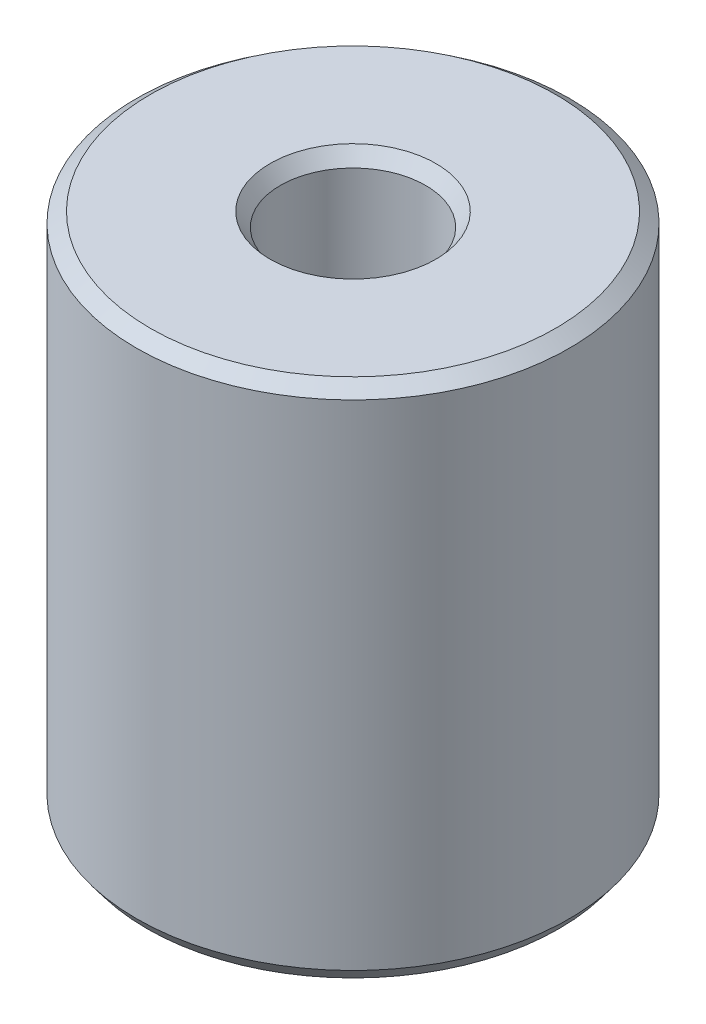
SolidWorks part; units mm, degrees
ref_plane "Front Plane" through (0, 0, 0) normal (0, 0, 1) x (1, 0, 0)
ref_plane "Top Plane" through (0, 0, 0) normal (0, 1, 0) x (1, 0, 0)
ref_plane "Right Plane" through (0, 0, 0) normal (1, 0, 0) x (0, 0, -1)
sketch "Sketch1" plane through (0, 0, 0) normal (0, 1, 0) x (1, 0, 0)
  circle A0 centre (0, 0) radius 10
  dimension "SLEEVE_OD" = 20
extrude "Boss-Extrude1" add sketch "Sketch1" along normal blind 23.9437
sketch "Sketch2" plane through (0, 0, 0) normal (0, 1, 0) x (1, 0, 0)
  circle A0 centre (0, 0) radius 3.3563
  dimension "BORE_D" = 6.7126
extrude "Cut-Extrude1" cut sketch "Sketch2" along normal through all
chamfer "Chamfer1" distance 0.4767 angle 53.199 4 edges at (0, 23.9437, 3.3563) (0, 0, 3.3563) (0, 0, 10) (0, 23.9437, 10) first distance on face at (0, 23.9437, 3.3563) first distance on face at (0, 0, 3.3563) first distance on face at (0, 23.9437, 10)
